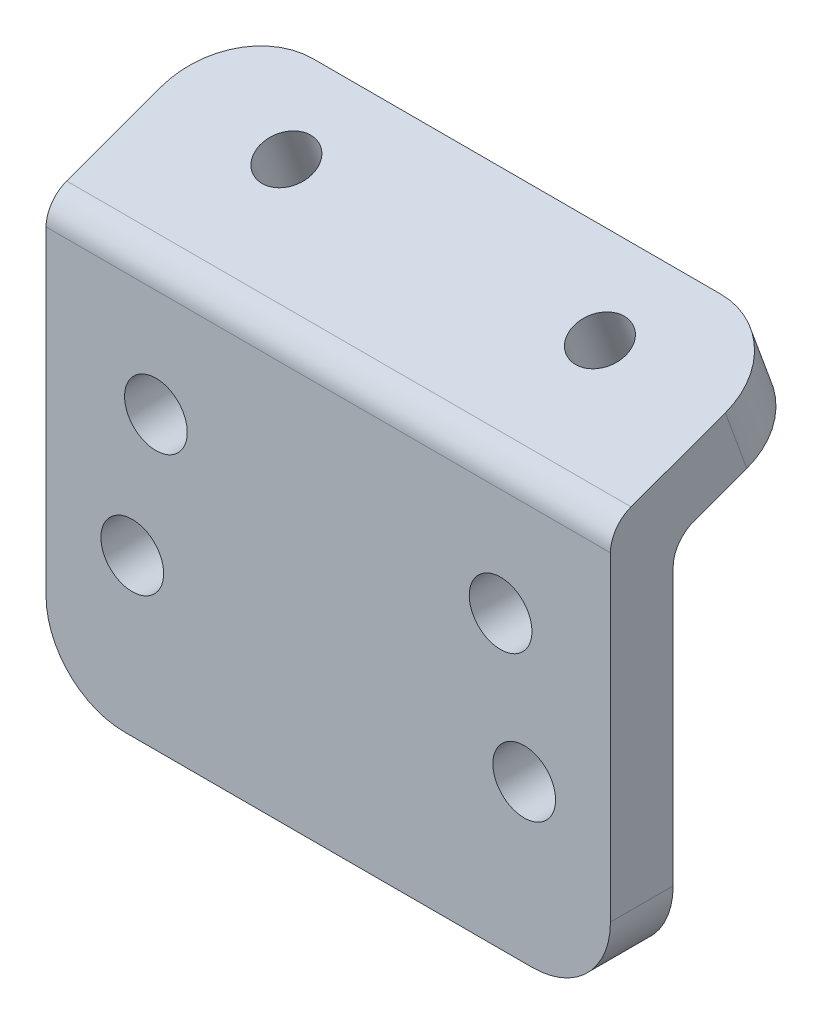
SolidWorks part; units mm, degrees
ref_plane "Plan de face" through (0, 0, 0) normal (0, 0, 1) x (1, 0, 0)
ref_plane "Plan de dessus" through (0, 0, 0) normal (0, 1, 0) x (1, 0, 0)
ref_plane "Plan de droite" through (0, 0, 0) normal (1, 0, 0) x (0, 0, -1)
sketch "Esquisse1" plane through (0, 0, 0) normal (0, 0, 1) x (1, 0, 0)
  line L1 (0, 0) -> (36, 0)
  line L2 (0, 0) -> (0, 24)
  line L3 (0, 24) -> (36, 24)
  line L4 (36, 0) -> (36, 24)
  dimension "D1" = 36
  dimension "D2" = 24
extrude "Boss.-Extru.1" add sketch "Esquisse1" along normal blind 4
sketch "Esquisse2" plane through (0, 0, 4) normal (0, 0, 1) x (1, 0, 0)
  line L0 (18, 0) -> (18, 24) construction
  line L1 (0, 0) -> (36, 0) construction
  line L2 (36, 24) -> (0, 24) construction
  line L3 (5.5, 10) -> (28.9923, 18.5505) construction
  line L4 (5.5, 10) -> (18, 10) construction
  circle A0 centre (5.5, 10) radius 2
  circle A1 centre (30.5, 10) radius 2
  circle A2 centre (28.9923, 18.5505) radius 2
  circle A3 centre (7.0077, 18.5505) radius 2
  dimension "D1" = 25
  dimension "D2" = 10
  dimension "D3" = 4
  dimension "D5" = 25
  dimension "D4" = 20
extrude "Enlèv. mat.-Extru.1" cut sketch "Esquisse2" against normal through all both and the other way through all
sketch "Esquisse3" plane through (36, 0, 0) normal (1, 0, 0) x (0, 0, -1)
  line L0 (0, 24) -> (9.3969, 27.4202)
  line L1 (9.3969, 27.4202) -> (8.0288, 31.179)
  line L2 (8.0288, 31.179) -> (-4, 26.8008)
  line L4 (-4, 26.8008) -> (-4, 24)
  line L5 (0, 0) -> (0, 24) construction
  line L6 (0, 24) -> (-4, 24)
  dimension "D1" = 4
  dimension "D2" = 10
  dimension "D3" = 110
extrude "Boss.-Extru.2" add sketch "Esquisse3" against normal up to vertex (36 mm away) up to point (0, 24, 0)
sketch "Esquisse4" plane through (0, 21.1925, 7.7135) normal (0, -0.9397, -0.342) x (1, 0, 0)
  line L0 (18, -18.2085) -> (18, -15.2024) construction
  line L1 (0, -18.2085) -> (36, -18.2085) construction
  circle A0 centre (8, -13.2085) radius 1.65
  circle A1 centre (28, -13.2085) radius 1.65
  dimension "D2" = 3.3
  dimension "D3" = 5
  dimension "D1" = 10
extrude "Enlèv. mat.-Extru.2" cut sketch "Esquisse4" against normal through all both and the other way through all
fillet "Congé2" radius 5 4 edges at (0, 29.2996, -8.7129) (36, 29.2996, -8.7129) (0, 0, 2) (36, 0, 2)
fillet "Congé3" radius 2 2 edges at (18, 26.8008, 4) (18, 24, 0)
